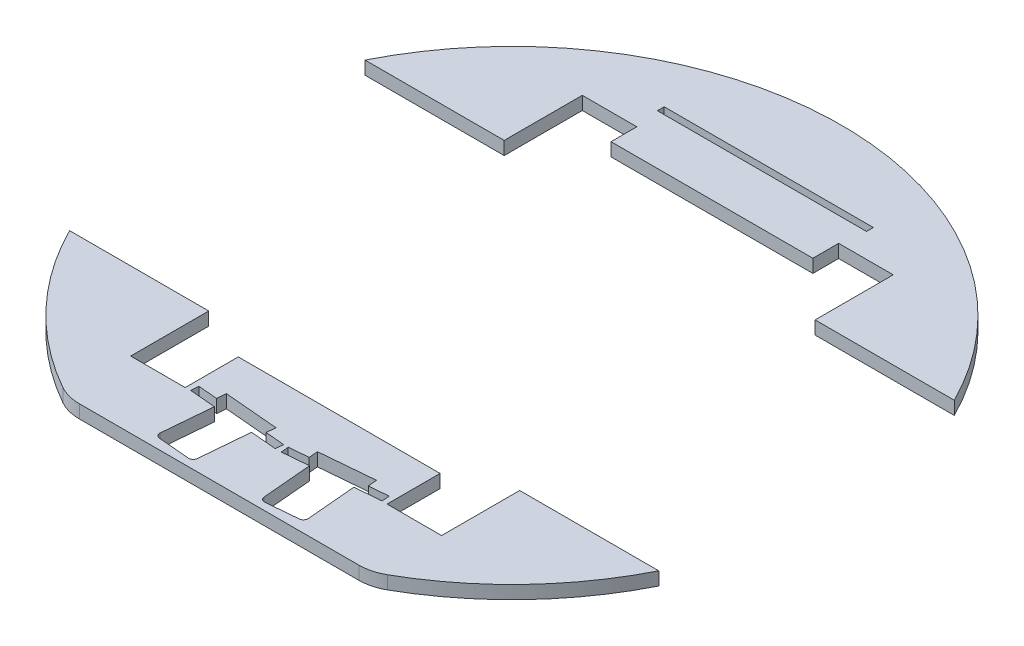
SolidWorks part; units mm, degrees
ref_plane "Front Plane" through (0, 0, 0) normal (0, 0, 1) x (1, 0, 0)
ref_plane "Top Plane" through (0, 0, 0) normal (0, 1, 0) x (1, 0, 0)
ref_plane "Right Plane" through (0, 0, 0) normal (1, 0, 0) x (0, 0, -1)
sketch "Sketch1" plane through (0, 0, 0) normal (0, 1, 0) x (1, 0, 0)
  line L0 (-30.7634, -64.4046) -> (30.7634, -64.4046)
  line L1 (0, -83.2398) -> (0, 0) construction
  line L2 (0, -83.2398) -> (33.2911, -64.4046) construction
  arc A0 (35.6856, -63.1093) -> (-35.6856, -63.1093) centre (0, 0) ccw
  circle A1 centre (0, -83.2398) radius 38.25 construction
  arc A2 (30.7634, -64.4046) -> (35.6856, -63.1093) centre (30.7634, -54.4046) ccw
  arc A3 (-30.7634, -64.4046) -> (-35.6856, -63.1093) centre (-30.7634, -54.4046) cw
  dimension "D1" = 145
  dimension "D2" = 76.5
  dimension "D4" = 10
  dimension "D3" = 60.5
extrude "Boss-Extrude1" add sketch "Sketch1" along normal blind 2.9
sketch "Sketch2" plane through (0, 2.9, 0) normal (0, 1, 0) x (1, 0, 0)
  line L29 (-22.2, -49.6757) -> (-22.2, -32.5) construction
  line L30 (-22.2, -49.6757) -> (-22.2, -32.5) construction
  line L38 (-34.2, -49.6757) -> (-22.2, -49.6757) construction
  line L39 (-34.2, -49.6757) -> (-34.2, 49.6757) construction
  line L40 (-34.2, 49.6757) -> (-22.2, 49.6757) construction
  line L41 (-22.2, 32.5) -> (-22.2, 49.6757) construction
  line L47 (22.2, 32.5) -> (22.2, 49.6757) construction
  line L48 (34.2, 49.6757) -> (22.2, 49.6757) construction
  line L49 (34.2, -49.6757) -> (34.2, 49.6757) construction
  line L50 (34.2, -49.6757) -> (22.2, -49.6757) construction
  line L51 (22.2, -49.6757) -> (22.2, -32.5) construction
  line L52 (22.2, -49.6757) -> (22.2, -32.5) construction
  line L53 (-22.2, -49.6757) -> (-22.2, -38) construction
  line L54 (-22.2, -49.6757) -> (-22.2, -38)
  line L55 (-22.2, 44) -> (22.2, 44)
  line L62 (-34.2, -49.6757) -> (-22.2, -49.6757)
  line L63 (-34.2, -49.6757) -> (-34.2, 49.6757)
  line L64 (-34.2, 49.6757) -> (-22.2, 49.6757)
  line L65 (-22.2, 44) -> (-22.2, 49.6757)
  line L71 (22.2, 44) -> (22.2, 49.6757)
  line L72 (34.2, 49.6757) -> (22.2, 49.6757)
  line L73 (34.2, -49.6757) -> (34.2, 49.6757)
  line L74 (34.2, -49.6757) -> (22.2, -49.6757)
  line L75 (22.2, -49.6757) -> (22.2, -38) construction
  line L76 (22.2, -49.6757) -> (22.2, -38)
  line L77 (-22.2, -38) -> (22.2, -38)
  dimension "D1" = 38
  dimension "D2" = 44
extrude "Cut-Extrude1" cut sketch "Sketch2" against normal through all contours L54 L77 L76 L74 L73 L72 L71 L55 L65 L64 L63 L62 region at (0, 2.9, -1.8128)
sketch "Sketch3" plane through (0, 2.9, 0) normal (0, 1, 0) x (1, 0, 0)
  line L0 (-34.2, 32.5) -> (-34.2, -32.5)
  line L1 (-72.5, -32.5) -> (-34.2, -32.5)
  line L2 (-72.5, -32.5) -> (-72.5, 32.5)
  line L3 (-72.5, 32.5) -> (-34.2, 32.5)
  line L4 (72.5, -32.5) -> (72.5, 32.5)
  line L5 (-72.5, -32.5) -> (72.5, 32.5) construction
  line L6 (-72.5, 32.5) -> (72.5, -32.5) construction
  line L8 (34.2, 32.5) -> (34.2, -32.5)
  line L10 (34.2, 32.5) -> (72.5, 32.5)
  line L11 (34.2, -32.5) -> (72.5, -32.5)
  line L12 (-34.2, -49.6757) -> (-34.2, 49.6757) construction
  line L13 (34.2, -49.6757) -> (34.2, 49.6757) construction
  arc A0 (35.6856, -63.1093) -> (-35.6856, -63.1093) centre (0, 0) ccw construction
  point P0 (0, 0)
  dimension "D1" = 65
extrude "Cut-Extrude2" cut sketch "Sketch3" against normal through all
sketch "Sketch4" plane through (0, 2.9, 0) normal (0, 1, 0) x (1, 0, 0)
  line L0 (-21.0702, -49.6179) -> (-0.6482, -51.4046)
  line L1 (21.0702, -49.6179) -> (20.922, -47.9244)
  line L2 (0.6482, -51.4046) -> (0.5, -49.7111)
  line L3 (20.922, -47.9244) -> (0.5, -49.7111)
  line L4 (0, 0) -> (0, -64.4046) construction
  line L5 (-30.7634, -64.4046) -> (30.7634, -64.4046) construction
  line L6 (-20.922, -47.9244) -> (-0.5, -49.7111)
  line L7 (-0.6482, -51.4046) -> (-0.5, -49.7111)
  line L8 (-21.0702, -49.6179) -> (-20.922, -47.9244)
  line L14 (21.0702, -49.6179) -> (0.6482, -51.4046)
  dimension "D1" = 1.7
  dimension "D2" = 20.5
  dimension "D3" = 5
  dimension "D4" = 13
  dimension "D5" = 0.5
extrude "Cut-Extrude3" cut sketch "Sketch4" against normal through all
sketch "Sketch5" plane through (0, 2.9, 0) normal (0, 1, 0) x (1, 0, 0)
  line L0 (6.3763, -50.9035) -> (15.342, -50.1191)
  line L1 (6.3763, -50.9035) -> (7.335, -61.8616)
  line L2 (15.342, -50.1191) -> (16.3007, -61.0772)
  line L3 (8.4183, -62.7706) -> (15.3917, -62.1605)
  line L4 (0.6482, -51.4046) -> (21.0702, -49.6179) construction
  line L5 (16.6882, -48.2948) -> (4.7338, -49.3407)
  line L6 (16.6882, -48.2948) -> (16.5139, -46.3024)
  line L7 (4.7338, -49.3407) -> (4.5595, -47.3483)
  line L8 (16.5139, -46.3024) -> (4.5595, -47.3483)
  line L9 (20.922, -47.9244) -> (0.5, -49.7111) construction
  line L10 (0, -38) -> (0, -64.4046) construction
  line L12 (-30.7634, -64.4046) -> (30.7634, -64.4046) construction
  line L13 (-16.5139, -46.3024) -> (-4.5595, -47.3483)
  line L14 (-4.7338, -49.3407) -> (-4.5595, -47.3483)
  line L15 (-16.6882, -48.2948) -> (-16.5139, -46.3024)
  line L16 (-16.6882, -48.2948) -> (-4.7338, -49.3407)
  line L17 (-8.4183, -62.7706) -> (-15.3917, -62.1605)
  line L18 (-15.342, -50.1191) -> (-16.3007, -61.0772)
  line L19 (-6.3763, -50.9035) -> (-7.335, -61.8616)
  line L20 (-6.3763, -50.9035) -> (-15.342, -50.1191)
  line L21 (-22.2, -38) -> (22.2, -38) construction
  arc A0 (16.3007, -61.0772) -> (15.3917, -62.1605) centre (15.3046, -61.1643) cw
  arc A1 (7.335, -61.8616) -> (8.4183, -62.7706) centre (8.3312, -61.7744) ccw
  arc A2 (-7.335, -61.8616) -> (-8.4183, -62.7706) centre (-8.3312, -61.7744) cw
  arc A3 (-16.3007, -61.0772) -> (-15.3917, -62.1605) centre (-15.3046, -61.1643) ccw
  point P14 (10.711, -48.8177)
  point P15 (10.711, -48.8177)
  point P17 (10.8592, -50.5113)
  point P18 (10.8592, -50.5113)
  point P21 (16.3879, -62.0734)
  point P24 (7.4222, -62.8578)
  point P40 (-7.4222, -62.8578)
  point P41 (-16.3879, -62.0734)
  dimension "D5" = 1
  dimension "D1" = 12
  dimension "D2" = 9
  dimension "D3" = 12
  dimension "D4" = 2
extrude "Cut-Extrude4" cut sketch "Sketch5" against normal through all
sketch "Sketch6" plane through (0, 2.9, 0) normal (0, 1, 0) x (1, 0, 0)
  line L0 (0, 0) -> (0, 55) construction
  line L1 (-23, 56.5) -> (23, 56.5)
  line L2 (-23, 56.5) -> (-23, 55)
  line L3 (-23, 55) -> (23, 55)
  line L4 (23, 56.5) -> (23, 55)
  dimension "D1" = 1.5
  dimension "D2" = 46
  dimension "D3" = 55
extrude "Cut-Extrude5" cut sketch "Sketch6" against normal through all
equation "\"smallPulleyTeeth\"= 15"
equation "\"largePulleyTeeth\"= 30"
equation "\"eighthThick\"= 2.9mm"
equation "\"sixteenthThick\" = 1.7mm"
equation "\"quarterThick\"=6.0mm"
equation "\"OD\" = 145mm"
equation "\"puckAngle\" = 60.5deg"
equation "\"puckDiam\" = 76.5mm"
equation "\"axlePress\" = 5.9mm"
equation "\"press\" = 0.2mm"
equation "\"wheelClear\" = 0.3mm"
equation "\"10-32clear\" = 4.8mm"
equation "\"6-32clear\" = 3.3mm"
equation "\"8-32clear\" = 4.0mm"
equation "\"4-40clear\" = 3.0mm"
equation "\"wheelHeight\" = 22mm"
equation "\"wheelWell\" = 65mm"
equation "\"D1@Sketch1\"=\"OD\""
equation "\"D1@Boss-Extrude1\"=\"eighthThick\""
equation "\"D2@Sketch1\"=\"puckDiam\""
equation "\"D3@Sketch1\"=\"puckAngle\""
equation "\"D1@Sketch3\"=\"wheelWell\""
